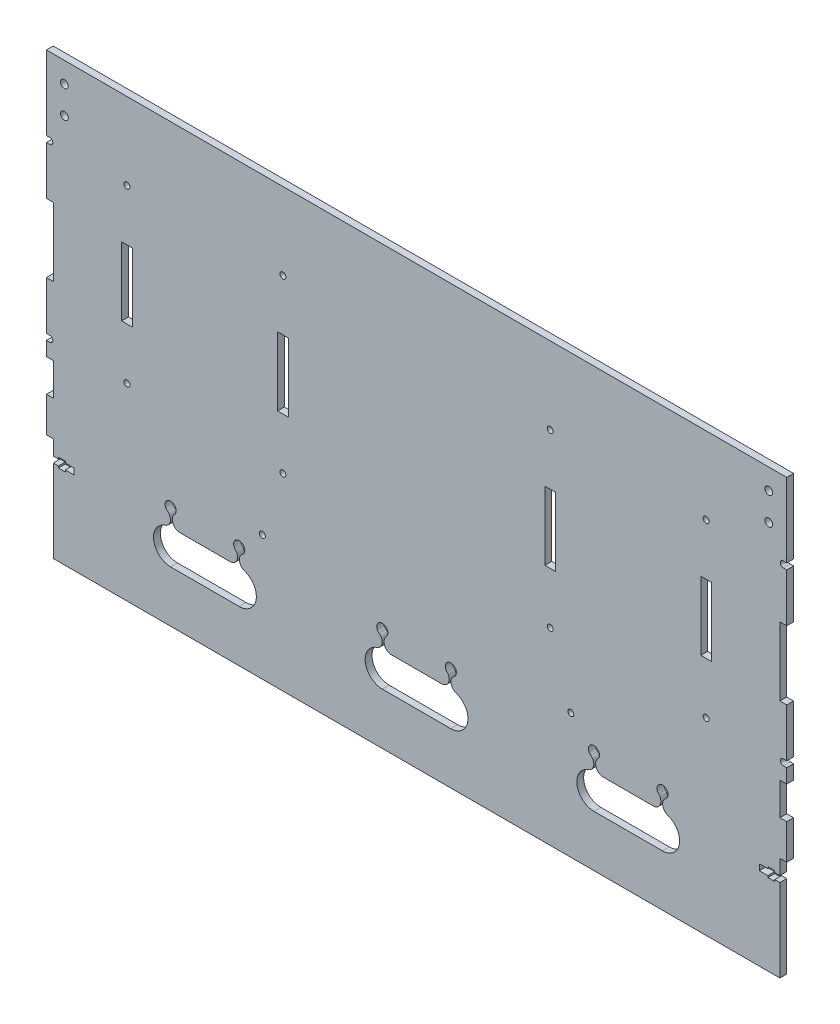
SolidWorks part; units mm, degrees
material "1060 Alloy"
ref_plane "Front Plane" through (0, 0, 0) normal (0, 0, 1) x (1, 0, 0)
ref_plane "Top Plane" through (0, 0, 0) normal (0, 1, 0) x (1, 0, 0)
ref_plane "Right Plane" through (0, 0, 0) normal (1, 0, 0) x (0, 0, -1)
sketch "Sketch1" plane through (0, 0, 0) normal (0, 0, 1) x (1, 0, 0)
  line L0 (216, -127.5) -> (-216, 127.5) construction
  line L1 (-216, 127.5) -> (216, 127.5)
  line L2 (-216, 127.5) -> (-216, -127.5)
  line L3 (-216, -127.5) -> (216, -127.5)
  line L4 (216, 127.5) -> (216, -127.5)
  dimension "D1" = 255
  dimension "D2" = 432
sheet metal parameters "Sheet-Metal1" thickness 4 parameters "D1"=5
base flange "Base-Flange1" sketch "Sketch1" thickness 4 reverse thickness direction no parameters "D1"=5
sketch "Sketch4" plane through (0, 0, 0) normal (0, 0, 1) x (1, 0, 0)
  line L0 (-78, 82.5) -> (-169, 82.5) construction
  line L1 (-169, 82.5) -> (-214, 82.5) construction
  line L2 (-214, 82.5) -> (-214, -17.5) construction
  line L3 (-214, -17.5) -> (-169, -17.5) construction
  line L4 (-169, -17.5) -> (-78, -17.5) construction
  line L5 (-78, -17.5) -> (-78, 82.5) construction
  line L6 (-169, 82.5) -> (-169, -17.5) construction
  line L7 (-78, -17.5) -> (78, -17.5) construction
  line L8 (0, -17.5) -> (0, 0) construction
  line L9 (216, 127.5) -> (-216, 127.5) construction
  line L10 (169, 82.5) -> (169, -17.5) construction
  line L11 (78, -17.5) -> (78, 82.5) construction
  line L12 (169, -17.5) -> (78, -17.5) construction
  line L13 (214, -17.5) -> (169, -17.5) construction
  line L14 (214, 82.5) -> (214, -17.5) construction
  line L15 (169, 82.5) -> (214, 82.5) construction
  line L16 (78, 82.5) -> (169, 82.5) construction
  line L17 (-81.15, 52.5) -> (-74.85, 12.5) construction
  line L18 (-216, 52.5) -> (-212, 52.5)
  line L19 (-216, 52.5) -> (-216, 12.5)
  line L20 (-216, 12.5) -> (-212, 12.5)
  line L21 (-212, 52.5) -> (-212, 12.5)
  line L22 (-172.15, 52.5) -> (-165.85, 52.5)
  line L23 (-172.15, 52.5) -> (-172.15, 12.5)
  line L24 (-172.15, 12.5) -> (-165.85, 12.5)
  line L25 (-165.85, 52.5) -> (-165.85, 12.5)
  line L26 (-81.15, 52.5) -> (-74.85, 52.5)
  line L27 (-81.15, 52.5) -> (-81.15, 12.5)
  line L28 (-81.15, 12.5) -> (-74.85, 12.5)
  line L29 (-74.85, 52.5) -> (-74.85, 12.5)
  line L30 (-165.85, 12.5) -> (-172.15, 52.5) construction
  line L31 (-216, 52.5) -> (-212, 12.5) construction
  line L32 (216, 52.5) -> (212, 12.5) construction
  line L33 (165.85, 12.5) -> (172.15, 52.5) construction
  line L34 (81.15, 52.5) -> (74.85, 12.5) construction
  line L35 (169, 82.5) -> (169, -17.5) construction
  line L36 (78, -17.5) -> (78, 82.5) construction
  line L37 (214, 82.5) -> (214, -17.5) construction
  line L38 (74.85, 52.5) -> (74.85, 12.5)
  line L39 (81.15, 12.5) -> (74.85, 12.5)
  line L40 (81.15, 52.5) -> (81.15, 12.5)
  line L41 (81.15, 52.5) -> (74.85, 52.5)
  line L42 (165.85, 52.5) -> (165.85, 12.5)
  line L43 (172.15, 12.5) -> (165.85, 12.5)
  line L44 (172.15, 52.5) -> (172.15, 12.5)
  line L45 (172.15, 52.5) -> (165.85, 52.5)
  line L46 (212, 52.5) -> (212, 12.5)
  line L47 (216, 12.5) -> (212, 12.5)
  line L48 (216, 52.5) -> (216, 12.5)
  line L49 (216, 52.5) -> (212, 52.5)
  circle A0 centre (-78, 82.5) radius 1.75
  circle A1 centre (214, -17.5) radius 1.75
  circle A2 centre (214, 82.5) radius 1.75
  circle A3 centre (-78, -17.5) radius 1.75
  circle A4 centre (-169, -17.5) radius 1.75
  circle A5 centre (-169, 82.5) radius 1.75
  circle A6 centre (-214, 82.5) radius 1.75
  circle A7 centre (-214, -17.5) radius 1.75
  circle A8 centre (169, 82.5) radius 1.75
  circle A9 centre (169, -17.5) radius 1.75
  circle A10 centre (78, -17.5) radius 1.75
  circle A11 centre (78, 82.5) radius 1.75
  point P29 (-214, 32.5)
  point P30 (-169, 32.5)
  point P31 (-78, 32.5)
  point P56 (78, 32.5)
  point P57 (169, 32.5)
  point P58 (214, 32.5)
  dimension "D3" = 3.5
  dimension "D1" = 45
  dimension "D2" = 100
  dimension "D4" = 78
  dimension "D5" = 91
  dimension "D6" = 45
  dimension "D7" = 6.3
  dimension "D8" = 40
  dimension "D9" = 4
extrude "Cut-Extrude1" cut sketch "Sketch4" against normal through all normal cut yes
sketch "Sketch5" plane through (0, 0, 0) normal (0, 0, 1) x (1, 0, 0)
  line L0 (-214, 82.5) -> (-216, 82.5) construction
  line L1 (-216, 127.5) -> (-216, 52.5) construction
  line L2 (-214, 80.75) -> (-216, 80.75)
  line L3 (-214, 84.25) -> (-216, 84.25)
  line L4 (-214, -17.5) -> (-216, -17.5) construction
  line L5 (-216, 12.5) -> (-216, -127.5) construction
  line L6 (-214, -19.25) -> (-216, -19.25)
  line L7 (-214, -15.75) -> (-216, -15.75)
  line L8 (0, 0) -> (0, 127.5) construction
  line L9 (216, 127.5) -> (-216, 127.5) construction
  line L10 (214, 82.5) -> (216, 82.5) construction
  line L11 (214, 80.75) -> (216, 80.75)
  line L12 (214, 84.25) -> (216, 84.25)
  line L13 (214, -17.5) -> (216, -17.5) construction
  line L14 (214, -19.25) -> (216, -19.25)
  line L15 (214, -15.75) -> (216, -15.75)
  arc A0 (-214, 80.75) -> (-214, 84.25) centre (-214, 82.5) ccw
  arc A1 (-216, 84.25) -> (-216, 80.75) centre (-216, 82.5) ccw
  circle A2 centre (-214, 82.5) radius 1.75 construction
  arc A3 (-214, -19.25) -> (-214, -15.75) centre (-214, -17.5) ccw
  arc A4 (-216, -15.75) -> (-216, -19.25) centre (-216, -17.5) ccw
  circle A5 centre (-214, -17.5) radius 1.75 construction
  arc A6 (214, 80.75) -> (214, 84.25) centre (214, 82.5) cw
  arc A7 (216, 84.25) -> (216, 80.75) centre (216, 82.5) cw
  arc A8 (214, -19.25) -> (214, -15.75) centre (214, -17.5) cw
  arc A9 (216, -15.75) -> (216, -19.25) centre (216, -17.5) cw
  point P5 (-215, 82.5)
  point P17 (-215, -17.5)
  point P31 (215, 82.5)
  point P38 (215, -17.5)
extrude "Cut-Extrude2" cut sketch "Sketch5" against normal through all normal cut yes
sketch "Sketch6" plane through (0, 0, 0) normal (0, 0, 1) x (1, 0, 0)
  line L0 (90, -54.5) -> (-90, -54.5) construction
  line L1 (0, -54.5) -> (0, 0) construction
  line L2 (216, 127.5) -> (-216, 127.5) construction
  circle A0 centre (-90, -54.5) radius 1.75
  circle A1 centre (90, -54.5) radius 1.75
  dimension "D2" = 3.5
  dimension "D1" = 180
  dimension "D3" = 182
extrude "Cut-Extrude3" cut sketch "Sketch6" against normal through all normal cut yes
sketch "Sketch7" plane through (0, 0, 0) normal (0, 0, 1) x (1, 0, 0)
  line L0 (205.5, 99.5) -> (205.5, 115.5) construction
  line L1 (216, 84.25) -> (216, 127.5) construction
  line L2 (216, 127.5) -> (-216, 127.5) construction
  line L3 (0, 0) -> (0, 112.8) construction
  line L4 (-205.5, 99.5) -> (-205.5, 115.5) construction
  circle A0 centre (205.5, 115.5) radius 2.25
  circle A1 centre (205.5, 99.5) radius 2.25
  circle A2 centre (-205.5, 99.5) radius 2.25
  circle A3 centre (-205.5, 115.5) radius 2.25
  dimension "D2" = 4.5
  dimension "D1" = 16
  dimension "D3" = 10.5
  dimension "D4" = 12
extrude "Cut-Extrude4" cut sketch "Sketch7" against normal up to next normal cut yes
sketch "Sketch8" plane through (0, 0, 0) normal (0, 0, 1) x (1, 0, 0)
  line L0 (-143.5, -67.5) -> (-103.5, -67.5) construction
  line L1 (-169, -17.5) -> (-78, -17.5) construction
  line L2 (-78, -17.5) -> (78, -17.5) construction
  line L3 (78, -17.5) -> (169, -17.5) construction
  line L4 (-123.5, -17.5) -> (-123.5, -67.5) construction
  line L5 (0, -17.5) -> (0, -67.5) construction
  line L6 (-20, -67.5) -> (20, -67.5) construction
  line L7 (123.5, -17.5) -> (123.5, -67.5) construction
  line L8 (103.5, -67.5) -> (143.5, -67.5) construction
  line L9 (-216, -127.5) -> (216, -127.5) construction
  circle A0 centre (-143.5, -67.5) radius 3.25
  circle A1 centre (-103.5, -67.5) radius 3.25
  circle A3 centre (-20, -67.5) radius 3.25
  circle A4 centre (20, -67.5) radius 3.25
  circle A5 centre (103.5, -67.5) radius 3.25
  circle A6 centre (143.5, -67.5) radius 3.25
  dimension "D1" = 6.5
  dimension "D2" = 40
  dimension "D3" = 60
extrude "Cut-Extrude5" cut sketch "Sketch8" against normal through all normal cut yes
sketch "Sketch9" plane through (0, 0, 0) normal (0, 0, 1) x (1, 0, 0)
  line L0 (-143.5, -87.5) -> (-103.5, -87.5) construction
  line L1 (-143.5, -77.5) -> (-103.5, -77.5)
  line L2 (-143.5, -97.5) -> (-103.5, -97.5)
  line L3 (0, 0) -> (0, -87.5) construction
  line L4 (-20, -87.5) -> (20, -87.5) construction
  line L5 (-20, -77.5) -> (20, -77.5)
  line L6 (-20, -97.5) -> (20, -97.5)
  line L7 (-20, -87.5) -> (-20, -67.5) construction
  line L8 (20, -67.5) -> (20, -87.5) construction
  line L9 (-103.5, -67.5) -> (-103.5, -87.5) construction
  line L10 (-143.5, -67.5) -> (-143.5, -87.5) construction
  line L11 (-103.5, -87.5) -> (-20, -87.5) construction
  line L12 (143.5, -87.5) -> (103.5, -87.5) construction
  line L13 (143.5, -77.5) -> (103.5, -77.5)
  line L14 (143.5, -97.5) -> (103.5, -97.5)
  line L15 (103.5, -87.5) -> (20, -87.5) construction
  line L16 (143.5, -67.5) -> (143.5, -87.5) construction
  line L17 (103.5, -67.5) -> (103.5, -87.5) construction
  arc A0 (-143.5, -77.5) -> (-143.5, -97.5) centre (-143.5, -87.5) ccw
  arc A1 (-103.5, -97.5) -> (-103.5, -77.5) centre (-103.5, -87.5) ccw
  arc A2 (-20, -77.5) -> (-20, -97.5) centre (-20, -87.5) ccw
  arc A3 (20, -97.5) -> (20, -77.5) centre (20, -87.5) ccw
  arc A4 (143.5, -77.5) -> (143.5, -97.5) centre (143.5, -87.5) cw
  arc A5 (103.5, -97.5) -> (103.5, -77.5) centre (103.5, -87.5) cw
  point P2 (-123.5, -87.5)
  point P12 (0, -87.5)
  point P31 (123.5, -87.5)
  dimension "D1" = 20
  dimension "D2" = 20
extrude "Cut-Extrude6" cut sketch "Sketch9" against normal through all normal cut yes
sketch "Sketch10" plane through (0, 0, 0) normal (0, 0, 1) x (1, 0, 0)
  line L0 (-216, 127.5) -> (-216, -127.5) construction
  line L1 (-216, -27.5) -> (-212, -27.5)
  line L2 (-216, -27.5) -> (-216, -127.5)
  line L3 (-216, -127.5) -> (-212, -127.5)
  line L4 (-212, -27.5) -> (-212, -127.5)
  line L5 (-216, -127.5) -> (216, -127.5) construction
  line L6 (216, -127.5) -> (216, -19.25) construction
  line L7 (216, -27.5) -> (212, -27.5)
  line L8 (216, -27.5) -> (216, -127.5)
  line L9 (216, -127.5) -> (212, -127.5)
  line L10 (212, -27.5) -> (212, -127.5)
  dimension "D1" = 100
  dimension "D2" = 4
extrude "Cut-Extrude7" cut sketch "Sketch10" against normal through all normal cut yes
sketch "Sketch11" plane through (0, 0, 0) normal (0, 0, 1) x (1, 0, 0)
  line L0 (-212, -75.75) -> (-209, -75.75)
  line L1 (-212, -127.5) -> (-212, -27.5) construction
  line L2 (-209, -75.75) -> (-209, -74.75)
  line L3 (-209, -74.75) -> (-205, -74.75)
  line L4 (-205, -74.75) -> (-205, -75.75)
  line L5 (-205, -75.75) -> (-200, -75.75)
  line L6 (-200, -75.75) -> (-200, -79.25)
  line L7 (-200, -79.25) -> (-205, -79.25)
  line L8 (-205, -79.25) -> (-205, -80.25)
  line L9 (-205, -80.25) -> (-209, -80.25)
  line L10 (-209, -80.25) -> (-209, -79.25)
  line L11 (-209, -79.25) -> (-212, -79.25)
  line L12 (-212, -79.25) -> (-212, -75.75)
  line L13 (-212, -77.5) -> (-200, -77.5) construction
  line L14 (-212, -127.5) -> (212, -127.5) construction
  line L15 (0, 0) -> (0, -127.5) construction
  line L16 (212, -77.5) -> (200, -77.5) construction
  line L17 (212, -79.25) -> (212, -75.75)
  line L18 (209, -79.25) -> (212, -79.25)
  line L19 (209, -80.25) -> (209, -79.25)
  line L20 (205, -80.25) -> (209, -80.25)
  line L21 (205, -79.25) -> (205, -80.25)
  line L22 (200, -79.25) -> (205, -79.25)
  line L23 (200, -75.75) -> (200, -79.25)
  line L24 (205, -75.75) -> (200, -75.75)
  line L25 (205, -74.75) -> (205, -75.75)
  line L26 (209, -74.75) -> (205, -74.75)
  line L27 (209, -75.75) -> (209, -74.75)
  line L28 (212, -75.75) -> (209, -75.75)
  dimension "D1" = 4
  dimension "D2" = 3
  dimension "D3" = 5
  dimension "D4" = 3.5
  dimension "D5" = 5.5
  dimension "D6" = 50
extrude "Cut-Extrude8" cut sketch "Sketch11" against normal through all normal cut yes
sketch "Sketch13" plane through (0, 0, 0) normal (0, 0, 1) x (1, 0, 0)
  line L0 (-212, -75.75) -> (-212, -27.5) construction
  line L1 (-212, -46.5) -> (-216, -46.5)
  line L2 (-212, -46.5) -> (-212, -67)
  line L3 (-212, -67) -> (-216, -67)
  line L4 (-216, -46.5) -> (-216, -67)
  line L5 (-212, -27.5) -> (-216, -27.5) construction
  line L6 (0, 0) -> (0, -53.4203) construction
  line L7 (216, -46.5) -> (216, -67)
  line L8 (212, -67) -> (216, -67)
  line L9 (212, -46.5) -> (212, -67)
  line L10 (212, -46.5) -> (216, -46.5)
  point P6 (-214, -27.5)
  dimension "D1" = 20.5
  dimension "D2" = 4
  dimension "D3" = 19
base flange "Tab1" sketch "Sketch13" thickness 4 reverse thickness direction no parameters "D1"=5
sketch "Sketch14" plane through (0, 0, 0) normal (0, 0, 1) x (1, 0, 0)
  line L0 (-103.5, -77.5) -> (-143.5, -77.5) construction
  line L1 (-123.5, -77.5) -> (-123.5, -61.5674) construction
  line L2 (-145.4244, -70.119) -> (-141.2103, -69.8065)
  line L3 (-146.6648, -78.014) -> (-138.0399, -77.5)
  line L4 (-105.7897, -69.8065) -> (-101.5756, -70.119)
  line L5 (-108.9601, -77.5) -> (-100.3352, -78.014)
  line L6 (-21.9244, -70.119) -> (-17.7103, -69.8065)
  line L7 (-23.1648, -78.014) -> (-14.5399, -77.5)
  line L8 (17.7103, -69.8065) -> (21.9244, -70.119)
  line L9 (14.5399, -77.5) -> (23.1648, -78.014)
  line L10 (0, -77.5) -> (0, -61.5674) construction
  line L11 (101.5756, -70.119) -> (105.7897, -69.8065)
  line L12 (100.3352, -78.014) -> (108.9601, -77.5)
  line L13 (141.2103, -69.8065) -> (145.4244, -70.119)
  line L14 (138.0399, -77.5) -> (146.6648, -78.014)
  line L15 (123.5, -77.5) -> (123.5, -61.5674) construction
  line L16 (20, -77.5) -> (-20, -77.5) construction
  arc A0 (-145.4244, -70.119) -> (-146.6648, -78.014) centre (-148.089, -73.7453) cw
  circle A1 centre (-143.5, -67.5) radius 3.25 construction
  arc A2 (-143.5, -77.5) -> (-143.5, -97.5) centre (-143.5, -87.5) ccw construction
  arc A3 (-141.2103, -69.8065) -> (-138.0399, -77.5) centre (-138.0399, -73) ccw
  arc A4 (-21.9244, -70.119) -> (-23.1648, -78.014) centre (-24.589, -73.7453) cw
  arc A5 (-105.7897, -69.8065) -> (-108.9601, -77.5) centre (-108.9601, -73) cw
  arc A6 (-101.5756, -70.119) -> (-100.3352, -78.014) centre (-98.911, -73.7453) ccw
  arc A7 (-17.7103, -69.8065) -> (-14.5399, -77.5) centre (-14.5399, -73) ccw
  arc A8 (17.7103, -69.8065) -> (14.5399, -77.5) centre (14.5399, -73) cw
  arc A9 (21.9244, -70.119) -> (23.1648, -78.014) centre (24.589, -73.7453) ccw
  arc A10 (101.5756, -70.119) -> (100.3352, -78.014) centre (98.911, -73.7453) cw
  arc A11 (105.7897, -69.8065) -> (108.9601, -77.5) centre (108.9601, -73) ccw
  arc A12 (141.2103, -69.8065) -> (138.0399, -77.5) centre (138.0399, -73) cw
  arc A13 (145.4244, -70.119) -> (146.6648, -78.014) centre (148.089, -73.7453) ccw
  dimension "D1" = 4.5
  dimension "D2" = 3
extrude "Cut-Extrude9" cut sketch "Sketch14" against normal up to next normal cut yes
flat pattern "Flat-Pattern1" [suppressed]
sketch "Bend-Lines1" plane through (0, 0, 0) normal (0, 1, 0) x (1, 0, 0)
sketch3d "Bounding-Box1" [suppressed]
  line L0 (-216, -127.5, 0) -> (216, -127.5, 0) construction
  line L1 (-216, 127.5, 0) -> (216, 127.5, 0) construction
  line L2 (-216, -127.5, 0) -> (-216, 127.5, 0) construction
  line L3 (216, -127.5, 0) -> (216, 127.5, 0) construction
